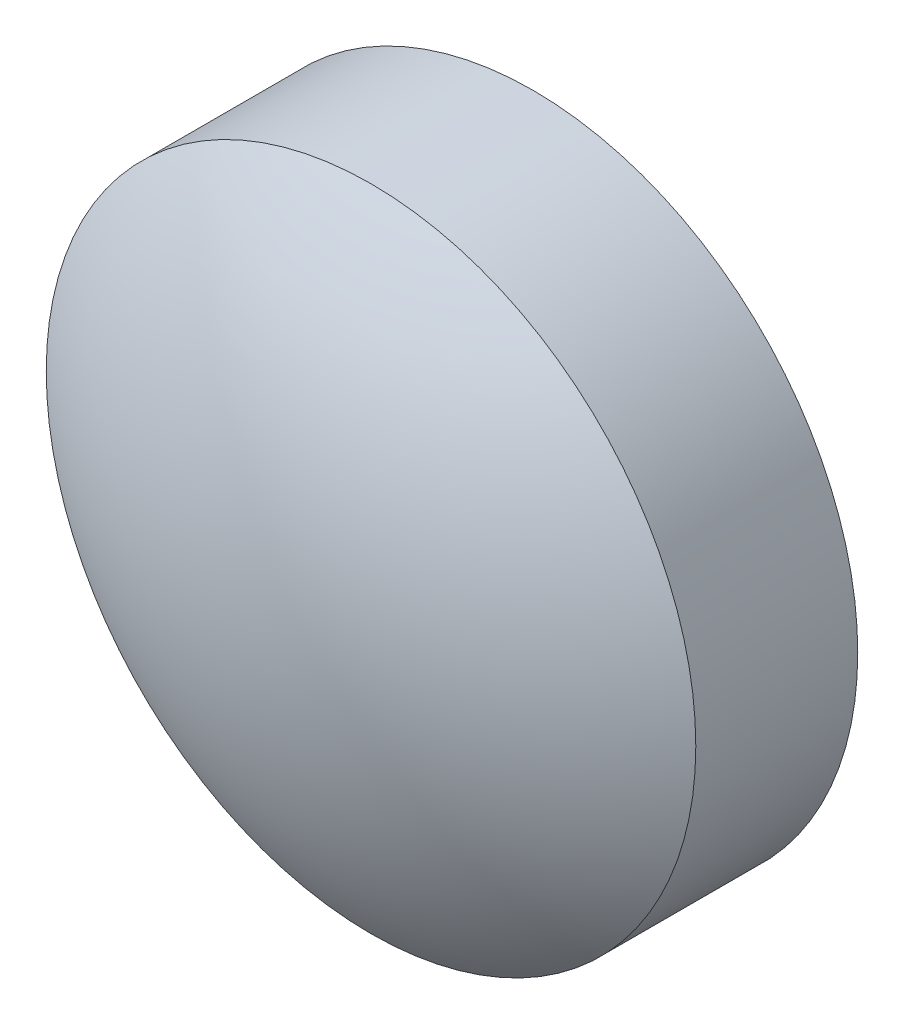
SolidWorks part; units mm, degrees
ref_plane "Ebene vorne" through (0, 0, 0) normal (0, 0, 1) x (1, 0, 0)
ref_plane "Ebene oben" through (0, 0, 0) normal (0, 1, 0) x (1, 0, 0)
ref_plane "Ebene rechts" through (0, 0, 0) normal (1, 0, 0) x (0, 0, -1)
sketch "Skizze1" plane through (0, 0, 0) normal (0, 1, 0) x (1, 0, 0)
  line L0 (3, 1.23) -> (0, 1.23)
  line L1 (0, 1.23) -> (0, -1.23)
  line L2 (3, -0.266) -> (3, 1.23)
  line L3 (0, 1.23) -> (0, -1.23) construction
  arc A0 (0, -1.23) -> (3, -0.266) centre (0, 3.92) ccw
revolve "Rotation1" add sketch "Skizze1" angle 360 about L3 reverse direction yes
ref_axis "ASS_Optical_Axis" through (0, 0, -1.23) along (0, 0, 1)
ref_plane "Ebene1" through (3, 0, 0) normal (1, 0, 0) x (0, 0, -1)
ref_plane "Ebene2" through (0, 0, -1.23) normal (0, 0, -1) x (-1, 0, 0)
ref_plane "Ebene3" through (0, 0, 0.266) normal (0, 0, 1) x (1, 0, 0)
ref_plane "Ebene4" through (0, 0, -0.482) normal (0, 0, 1) x (1, 0, 0)
ref_axis "Achse3" through (-3.3, 0, -0.482) along (1, 0, 0)
ref_point "Punkt2"
ref_plane "Ebene5" through (-3, 0, 0) normal (-1, 0, 0) x (0, 0, 1)
ref_point "Punkt3"
